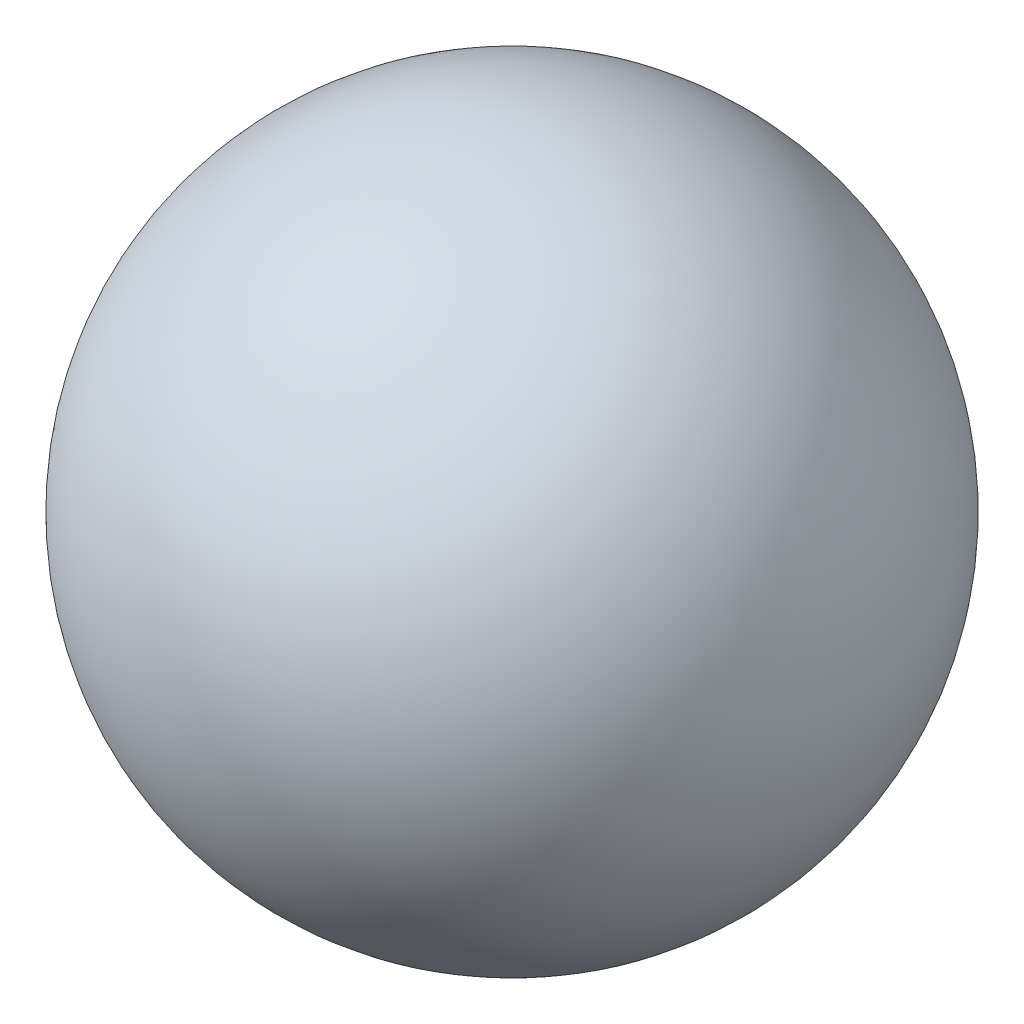
SolidWorks part; units mm, degrees
ref_plane "Front" through (0, 0, 0) normal (0, 0, 1) x (1, 0, 0)
ref_plane "Top" through (0, 0, 0) normal (0, 1, 0) x (1, 0, 0)
ref_plane "Right" through (0, 0, 0) normal (1, 0, 0) x (0, 0, -1)
sketch "Sketch1" plane through (0, 0, 0) normal (0, 0, 1) x (1, 0, 0)
  line L0 (0, 31.5) -> (0, -31.5) construction
  line L1 (0, 31.5) -> (0, -31.5)
  arc A0 (0, 31.5) -> (0, -31.5) centre (0, 0) cw
  dimension "D1" = 31.5
  dimension "D2" = 63
revolve "Revolve1" add sketch "Sketch1" angle 360 about L0
sketch "Sketch2" plane through (0, 0, 0) normal (0, 0, 1) x (1, 0, 0)
  circle A0 centre (0, 0) radius 31.5 construction
  point P0 (0, -31.5)
  point P1 (0, 0)
